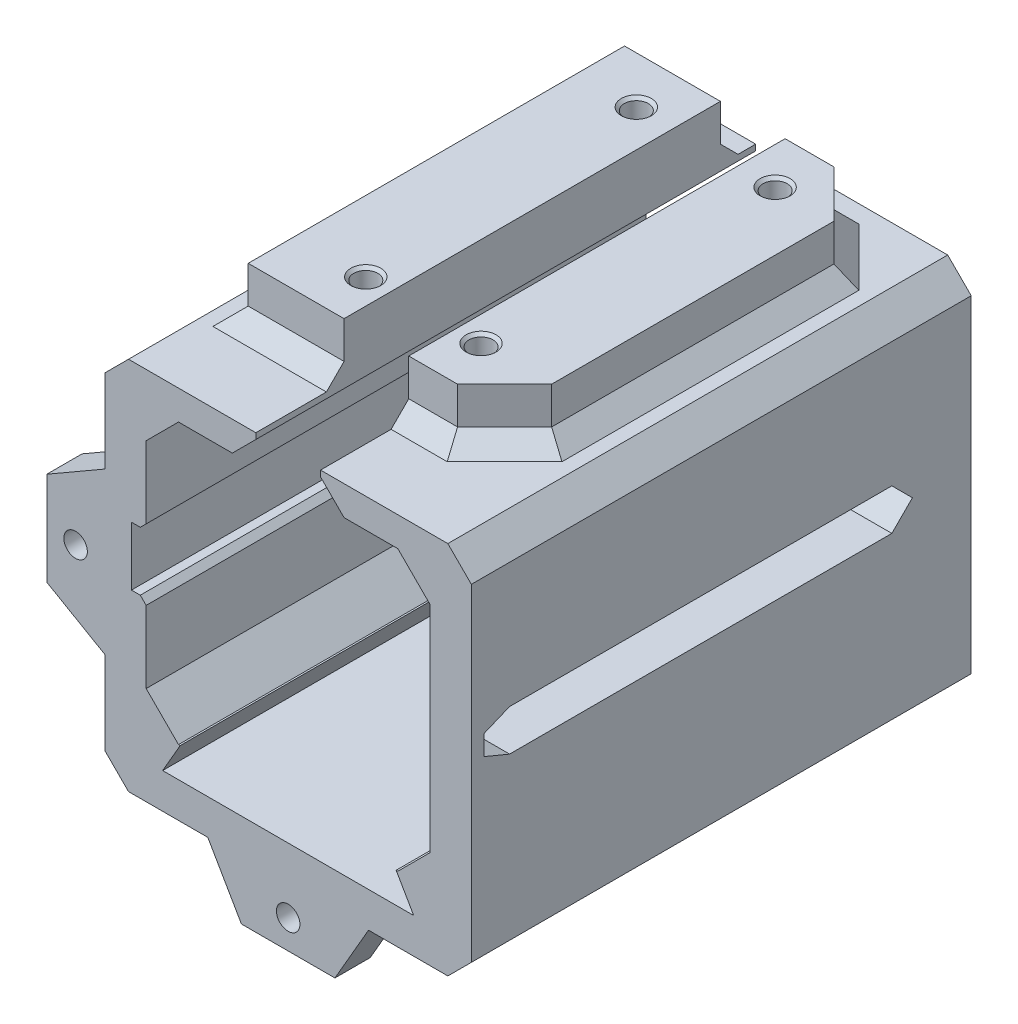
SolidWorks part; units mm, degrees
ref_plane "Front Plane" through (0, 0, 0) normal (0, 0, 1) x (1, 0, 0)
ref_plane "Top Plane" through (0, 0, 0) normal (0, 1, 0) x (1, 0, 0)
ref_plane "Right Plane" through (0, 0, 0) normal (1, 0, 0) x (0, 0, -1)
sketch "Sketch3" plane through (0, 0, 0) normal (0, 0, 1) x (1, 0, 0)
  line L0 (-20.15, 10.3748) -> (-23.65, 10.3748)
  line L1 (-23.65, 10.3748) -> (-23.65, 10.3393)
  line L2 (-23.65, 10.3393) -> (-18.1855, 4.8748)
  line L3 (-18.1855, 4.8748) -> (-21, 0)
  line L4 (-21, 0) -> (21, 0)
  line L5 (21, 0) -> (18.1855, 4.8748)
  line L6 (18.1855, 4.8748) -> (23.65, 10.3393)
  line L7 (23.65, 10.3393) -> (23.65, 10.3748)
  line L8 (23.65, 10.3748) -> (20.15, 10.3748)
  line L9 (20.15, 10.3748) -> (17.15, 7.3748)
  line L10 (17.15, 7.3748) -> (-17.15, 7.3748)
  line L11 (-17.15, 7.3748) -> (-20.15, 10.3748)
  point P12 (0, 0)
sketch "Sketch4" plane through (0, 0, 0) normal (0, 0, 1) x (1, 0, 0)
  line L3 (-18.3587, 4.9748) -> (-27, 4.9748)
  line L4 (-27, 4.9748) -> (-27, -6.2)
  line L5 (-27, -6.2) -> (27, -6.2)
  line L6 (21.3464, -0.2) -> (18.3587, 4.9748)
  line L7 (-21.3464, -0.2) -> (21.3464, -0.2)
  line L8 (-18.3587, 4.9748) -> (-21.3464, -0.2)
  line L9 (21.3464, -0.2) -> (18.3587, 4.9748)
  line L10 (-21.3464, -0.2) -> (21.3464, -0.2)
  line L11 (-18.3587, 4.9748) -> (-21.3464, -0.2)
  line L12 (27, -6.2) -> (27, 4.9748)
  line L13 (27, 4.9748) -> (18.3587, 4.9748)
  dimension "D2" = 36.7175
  dimension "D3" = 54
  dimension "D4" = 6
  dimension "D5" = 27
  dimension "D6" = 42.6928
  dimension "D7" = 60
  dimension "D8" = 11.1748
  dimension "D1" = 0.2
extrude "Boss-Extrude1" add sketch "Sketch4" along normal blind 100
sketch "Sketch6" plane through (0, 0, 100) normal (0, 0, 1) x (1, 0, 0)
  line L0 (-24.15, 4.9748) -> (-24.15, 52.4748)
  line L1 (-18.3587, 4.9748) -> (-27, 4.9748) construction
  line L2 (-24.15, 52.4748) -> (-5.5, 52.4748)
  line L3 (-5.5, 52.4748) -> (-5.5, 57.4748)
  line L4 (-5.5, 57.4748) -> (-31.15, 57.4748)
  line L5 (-31.15, 57.4748) -> (-31.15, -6.2)
  line L6 (-31.15, -6.2) -> (-24.15, -6.2)
  line L7 (-27, -6.2) -> (27, -6.2) construction
  line L8 (-24.15, -6.2) -> (-24.15, 4.9748)
  line L9 (-23.65, 46.5103) -> (-23.65, 34.3248) construction
  line L10 (-9, 51.9748) -> (-18.1855, 51.9748) construction
  line L12 (24.15, -6.2) -> (24.15, 52.4748)
  line L13 (-27, -6.2) -> (27, -6.2) construction
  line L14 (24.15, 52.4748) -> (5.5, 52.4748)
  line L15 (5.5, 52.4748) -> (5.5, 57.4748)
  line L16 (5.5, 57.4748) -> (31.15, 57.4748)
  line L17 (31.15, 57.4748) -> (31.15, -6.2)
  line L18 (31.15, -6.2) -> (24.15, -6.2)
  line L20 (23.65, 42.9748) -> (23.65, 46.5103) construction
  line L21 (5, 62.9748) -> (5, 55.9748) construction
  line L22 (-5, 55.9748) -> (-5, 62.9748) construction
  dimension "D1" = 7
  dimension "D2" = 0.5
  dimension "D3" = 0.5
  dimension "D4" = 5
  dimension "D5" = 0.5
  dimension "D6" = 5
  dimension "D7" = 0.5
  dimension "D8" = 7
  dimension "D9" = 0.5
extrude "Boss-Extrude2" add sketch "Sketch6" against normal up to surface (100 mm away) up to face at (0, 0.8874, 0)
sketch "Sketch7" plane through (31.15, 0, 0) normal (1, 0, 0) x (0, 0, -1)
  line L0 (-85, 28.7248) -> (-81.5, 25.2248)
  line L1 (-81.5, 25.2248) -> (-13.5, 25.2248)
  line L4 (-13.5, 32.2248) -> (-81.5, 32.2248)
  line L5 (-81.5, 32.2248) -> (-85, 28.7248)
  line L6 (-100, -6.2) -> (-100, 57.4748) construction
  line L7 (-13.5, 25.2248) -> (-10, 28.7248)
  line L8 (-10, 28.7248) -> (-13.5, 32.2248)
  line L9 (0, 57.4748) -> (0, -6.2) construction
  line L10 (-13.5, 25.2248) -> (0, 25.2248) construction
  line L11 (0, 32.2248) -> (-13.5, 32.2248) construction
  line L12 (0, 25.2248) -> (0, 32.2248) construction
  point P6 (0, 28.7248)
  dimension "D1" = 135
  dimension "D2" = 15
  dimension "D3" = 7
  dimension "D4" = 23.75
  dimension "D5" = 90
  dimension "D6" = 10
extrude "Cut-Extrude1" cut sketch "Sketch7" against normal blind 10
chamfer "Chamfer1" distance 5.5 angle 45 4 edges at (24.15, 4.9748, 50) (-24.15, 4.9748, 50) (-24.15, 52.4748, 50) (24.15, 52.4748, 50)
chamfer "Chamfer2" distance 4 angle 45 2 edges at (5.5, 52.4748, 50) (-5.5, 52.4748, 50)
sketch "Sketch8" plane through (0, 57.4748, 0) normal (0, 1, 0) x (1, 0, 0)
  line L0 (-5.5, -100) -> (-31.15, -100) construction
  line L1 (-21.8, -70) -> (13.8, -70)
  line L2 (-21.8, -70) -> (-21.8, -6)
  line L3 (-21.8, -6) -> (13.8, -6)
  line L4 (21.8, -62) -> (21.8, -14)
  line L5 (13.8, -70) -> (21.8, -62)
  line L6 (13.8, -6) -> (21.8, -14)
  circle A0 centre (9.8, -62) radius 2
  circle A1 centre (11.8, -14) radius 2
  circle A2 centre (-11.8, -14) radius 2
  circle A3 centre (-9.8, -62) radius 2
  point P1 (21.8, -6)
  point P3 (21.8, -70)
  dimension "D5" = 4
  dimension "D6" = 4
  dimension "D9" = 4
  dimension "D10" = 4
  dimension "D1" = 94
  dimension "D2" = 43.6
  dimension "D3" = 64
  dimension "D4" = 21.8
extrude "Boss-Extrude3" add sketch "Sketch8" along normal blind 9.3
sketch "Sketch9" plane through (0, 0, 0) normal (0, 0, 1) x (1, 0, 0)
  line L0 (-21.8, 66.7748) -> (13.8, 66.7748) construction
  line L1 (5.5, 57.4748) -> (-5.5, 57.4748)
  line L2 (5.5, 57.4748) -> (5.5, 66.7748)
  line L3 (5.5, 66.7748) -> (-5.5, 66.7748)
  line L4 (-5.5, 57.4748) -> (-5.5, 66.7748)
  line L5 (-5.5, 56.4748) -> (-5.5, 57.4748) construction
extrude "Cut-Extrude3" cut sketch "Sketch9" against normal blind 10 and the other way through all
chamfer "Chamfer3" distance 4 angle 45 4 edges at (31.15, -6.2, 50) (-31.15, -6.2, 50) (-31.15, 57.4748, 50) (31.15, 57.4748, 50)
chamfer "Chamfer4" distance 3 angle 45 8 edges at (9.65, 57.4748, 6) (17.8, 57.4748, 10) (21.8, 57.4748, 38) (17.8, 57.4748, 66) (9.65, 57.4748, 70) (-13.65, 57.4748, 6) (-13.65, 57.4748, 70) (-21.8, 57.4748, 38)
chamfer "Chamfer5" distance 3 3 edges at (27.65, 25.2248, 81.5) (27.65, 32.2248, 81.5) (27.65, 28.7248, 85)
sketch "Sketch10" plane through (0, 0, 100) normal (0, 0, 1) x (1, 0, 0)
  line L0 (-24.15, 10.4748) -> (-24.15, 46.9748) construction
  line L1 (-21.65, 23.7248) -> (-26.65, 23.7248)
  line L2 (-21.65, 23.7248) -> (-21.65, 33.7248)
  line L3 (-21.65, 33.7248) -> (-26.65, 33.7248)
  line L4 (-26.65, 23.7248) -> (-26.65, 33.7248)
  line L5 (-21.65, 23.7248) -> (-26.65, 33.7248) construction
  line L6 (-21.65, 33.7248) -> (-26.65, 23.7248) construction
  point P0 (-24.15, 28.7248)
  dimension "D1" = 5
  dimension "D2" = 10
extrude "Cut-Extrude4" cut sketch "Sketch10" against normal offset from surface (94 mm away) 6 up to face at (0, 29.896, 0)
chamfer "Chamfer7" distance 1 angle 45 1 edges at (-24.15, 28.7248, 6)
chamfer "Chamfer8" distance 1 angle 45 2 edges at (-24.15, 23.7248, 52.5) (-24.15, 33.7248, 52.5)
sketch "Sketch11" plane through (0, 66.7748, 0) normal (0, 1, 0) x (1, 0, 0)
  circle A0 centre (-11.8, -14) radius 2.05
  circle A1 centre (11.8, -14) radius 2.05
  circle A2 centre (-9.8, -62) radius 2.05
  circle A3 centre (9.8, -62) radius 2.05
  dimension "D1" = 4.1
  dimension "D2" = 4.1
  dimension "D3" = 4.1
  dimension "D4" = 4.1
extrude "Cut-Extrude5" cut sketch "Sketch11" against normal blind 10
chamfer "Chamfer9" distance 0.5 angle 45 4 edges at (11.8, 66.7748, 16.05) (-11.8, 66.7748, 16.05) (-9.8, 66.7748, 64.05) (9.8, 66.7748, 64.05)
sketch "Sketch12" plane through (0, 0, 0) normal (0, 0, 1) x (1, 0, 0)
  line L1 (-25, 52.7248) -> (25, 52.7248) construction
  line L2 (-25, 52.7248) -> (-25, 2.7248) construction
  line L3 (-25, 2.7248) -> (25, 2.7248) construction
  line L4 (25, 52.7248) -> (25, 2.7248) construction
  line L5 (24.15, 46.9748) -> (24.15, 10.4748) construction
  circle A0 centre (-25, 52.7248) radius 2
  circle A1 centre (25, 52.7248) radius 2
  circle A2 centre (-25, 2.7248) radius 2
  circle A3 centre (25, 2.7248) radius 2
  point P5 (0, 2.7248)
  point P9 (24.15, 28.7248)
  dimension "D1" = 4
  dimension "D5" = 4
  dimension "D6" = 4
  dimension "D7" = 4
  dimension "D2" = 50
  dimension "D3" = 50
  dimension "D4" = 24
extrude "Cut-Extrude6" cut sketch "Sketch12" along normal blind 15
sketch "Sketch20" plane through (0, 0, 100) normal (0, 0, 1) x (1, 0, 0)
  line L0 (31.15, -2.2) -> (31.15, 53.4748) construction
  line L1 (-31.15, 57.4748) -> (31.15, 57.4748)
  line L2 (-31.15, 57.4748) -> (-31.15, -6.2)
  line L3 (-31.15, -6.2) -> (31.15, -6.2)
  line L4 (31.15, 57.4748) -> (31.15, -6.2)
  line L5 (-5.5, 57.4748) -> (-27.15, 57.4748) construction
  line L6 (-31.15, 53.4748) -> (-31.15, -2.2) construction
  line L7 (-27.15, -6.2) -> (27.15, -6.2) construction
extrude "Cut-Extrude14" cut sketch "Sketch20" against normal blind 15
sketch "Sketch21" plane through (0, 0, 85) normal (0, 0, 1) x (1, 0, 0)
  line L0 (-31.15, 11.9716) -> (-41.05, 17.6874)
  line L1 (-31.15, 53.4748) -> (-31.15, -2.2) construction
  line L2 (-41.05, 17.6874) -> (-41.05, 33.5874)
  line L3 (-41.05, 33.5874) -> (-31.15, 39.3032)
  line L4 (-31.15, 39.3032) -> (-31.15, 11.9716)
  line L10 (-13.6658, -6.2) -> (-7.95, -16.1)
  line L11 (-27.15, -6.2) -> (27.15, -6.2) construction
  line L12 (-7.95, -16.1) -> (7.95, -16.1)
  line L13 (7.95, -16.1) -> (13.6658, -6.2)
  line L14 (13.6658, -6.2) -> (-13.6658, -6.2)
  point P6 (-31.15, 25.6374)
  point P7 (-41.05, 25.6374)
  point P14 (0, -6.2)
  point P15 (0, -16.1)
  point P16 (-17.3926, -6.2)
  dimension "D1" = 15.9
  dimension "D2" = 60
  dimension "D3" = 60
  dimension "D4" = 9.9
  dimension "D5" = 15.9
  dimension "D6" = 60
  dimension "D7" = 60
  dimension "D8" = 9.9
extrude "Boss-Extrude4" add sketch "Sketch21" against normal blind 6
sketch "Sketch22" plane through (0, 0, 85) normal (0, 0, 1) x (1, 0, 0)
  line L0 (-41.05, 33.5874) -> (-41.05, 17.6874) construction
  line L1 (-7.95, -16.1) -> (7.95, -16.1) construction
  circle A0 centre (-36.15, 25.6374) radius 2
  circle A1 centre (0, -11.2) radius 2
  point P6 (-41.05, 25.6374)
  point P7 (0, 0)
  dimension "D2" = 4
  dimension "D4" = 4
  dimension "D1" = 4.9
  dimension "D3" = 4.9
extrude "Cut-Extrude15" cut sketch "Sketch22" against normal blind 10
chamfer "Chamfer10" distance 1 angle 22.5 1 edges at (0, -6.2, 79)
chamfer "Chamfer11" distance 1 angle 22.5 1 edges at (-31.15, 25.6374, 79)
